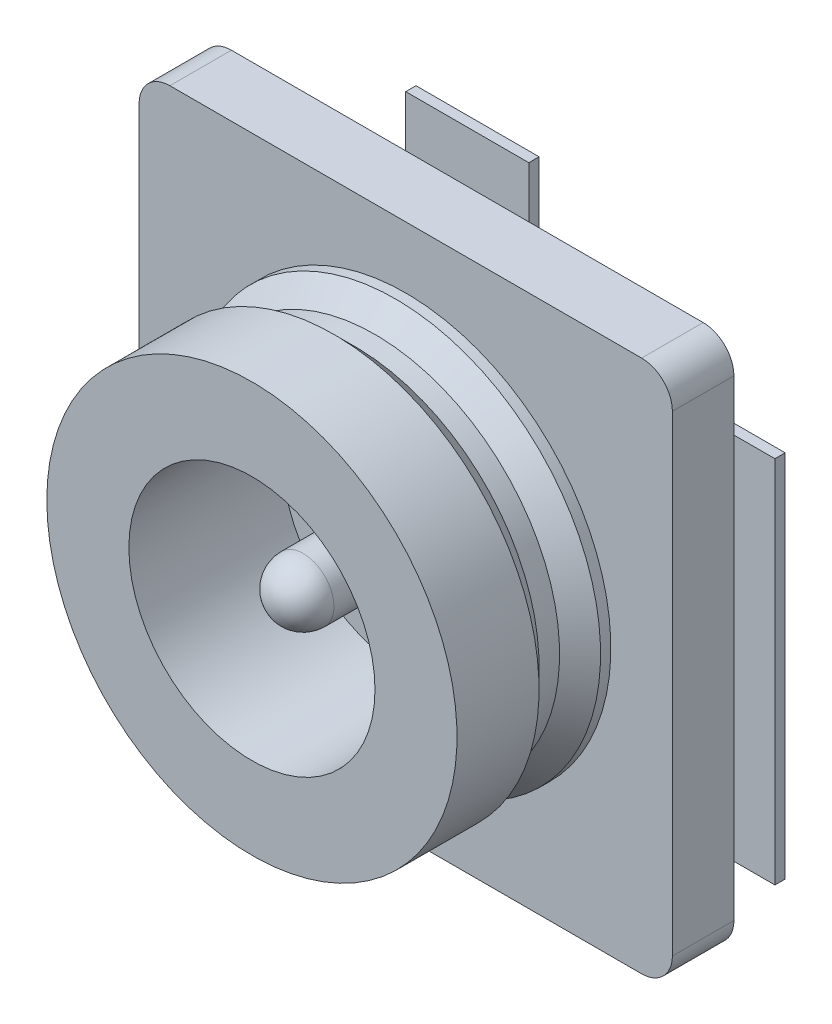
SolidWorks part; units mm, degrees
ref_plane "Front Plane" through (0, 0, 0) normal (0, 0, 1) x (1, 0, 0)
ref_plane "Top Plane" through (0, 0, 0) normal (0, 1, 0) x (1, 0, 0)
ref_plane "Right Plane" through (0, 0, 0) normal (1, 0, 0) x (0, 0, -1)
sketch "Sketch2" plane through (0, 0, 0) normal (0, 0, 1) x (1, 0, 0)
  line L1 (0, 0) -> (2.6, 0)
  line L2 (0, 0) -> (0, 2.6)
  line L3 (0, 2.6) -> (2.6, 2.6)
  line L4 (2.6, 0) -> (2.6, 2.6)
  dimension "D1" = 2.6
  dimension "D2" = 2.6
extrude "Boss-Extrude2" add sketch "Sketch2" along normal blind 0.3
fillet "Fillet1" radius 0.15 4 edges at (0, 0, 0.15) (2.6, 0, 0.15) (0, 2.6, 0.15) (2.6, 2.6, 0.15)
ref_plane "Plane1" through (0, 1.3, 0) normal (0, 1, 0) x (1, 0, 0)
ref_plane "Plane2" through (1.3, 0, 0) normal (1, 0, 0) x (0, 0, -1)
ref_axis "Axis1" through (1.3, 1.3, -0.0175) along (0, 0, -1)
sketch "Sketch3" plane through (0, 0, 0) normal (0, 0, 1) x (1, 0, 0)
  line L0 (0, 1.3) -> (2.6, 1.3) construction
  line L1 (-0.2, 2.2) -> (0.3, 2.2)
  line L2 (-0.2, 2.2) -> (-0.2, 0.4)
  line L3 (-0.2, 0.4) -> (0.3, 0.4)
  line L4 (0.3, 2.2) -> (0.3, 0.4)
  line L5 (2.3, 2.2) -> (2.8, 2.2)
  line L6 (2.3, 2.2) -> (2.3, 0.4)
  line L7 (2.3, 0.4) -> (2.8, 0.4)
  line L8 (2.8, 2.2) -> (2.8, 0.4)
  line L9 (0, 2.45) -> (0, 0.15) construction
  line L10 (2.6, 0.15) -> (2.6, 2.45) construction
  line L11 (1.475, 2.2) -> (1.6, 2.2)
  line L12 (2.45, 2.6) -> (0.15, 2.6) construction
  line L13 (1.3, 2.6) -> (1.3, 0) construction
  line L14 (0.15, 0) -> (2.45, 0) construction
  line L15 (1, 2.85) -> (1.6, 2.85)
  line L16 (1, 2.85) -> (1, 2.2)
  line L17 (1, 2.2) -> (1.125, 2.2)
  line L18 (1.6, 2.85) -> (1.6, 2.2)
  line L19 (1, 0.4) -> (1.6, 0.4)
  line L20 (1, 0.4) -> (1, -0.25)
  line L21 (1, -0.25) -> (1.6, -0.25)
  line L22 (1.6, 0.4) -> (1.6, -0.25)
  line L24 (1.125, 2.2) -> (1.125, 1.5437)
  line L26 (1.475, 2.2) -> (1.475, 1.5437)
  arc A0 (1.125, 1.5437) -> (1.475, 1.5437) centre (1.3, 1.3) ccw
  point P14 (2.3, 1.3)
  point P21 (0.3, 1.3)
  point P33 (1.3, 0.4)
  dimension "D6" = 0.6
  dimension "D1" = 3
  dimension "D2" = 0.5
  dimension "D3" = 0.5
  dimension "D4" = 1.8
  dimension "D5" = 0.6
  dimension "D7" = 3.1
  dimension "D8" = 0.35
extrude "Boss-Extrude3" add sketch "Sketch3" against normal blind 0.05
sketch "Sketch4" plane through (1.3, 0, 0) normal (1, 0, 0) x (0, 0, -1)
  line L0 (-0.3, 0.15) -> (-0.3, 2.45) construction
  line L1 (-0.3, 1.45) -> (-0.8, 1.45)
  line L2 (-0.3, 1.45) -> (-0.3, 1.3)
  line L3 (-0.3, 2.6) -> (-0.3, 2.45) construction
  line L4 (-0.95, 1.3) -> (-0.3, 1.3)
  line L5 (0.0607, 1.3) -> (-0.95, 1.3) construction
  line L6 (0.0175, 1.3) -> (0.3675, 1.3) construction
  line L7 (-0.3, 1.9) -> (-1.05, 1.9)
  line L8 (-0.3, 1.9) -> (-0.3, 2.3)
  line L9 (-0.3, 2.3) -> (-0.35, 2.3)
  line L10 (-1.05, 1.9) -> (-1.05, 2.3)
  line L11 (-0.55, 2.2) -> (-0.65, 2.3)
  line L14 (-0.45, 2.2) -> (-0.55, 2.2)
  line L16 (-0.45, 2.2) -> (-0.35, 2.3)
  line L17 (-0.65, 2.3) -> (-1.05, 2.3)
  arc A0 (-0.8, 1.45) -> (-0.95, 1.3) centre (-0.8, 1.3) ccw
  dimension "D5" = 0.15
  dimension "D1" = 1
  dimension "D2" = 0.6
  dimension "D3" = 0.75
  dimension "D4" = 0.65
  dimension "D6" = 225
  dimension "D7" = 225
  dimension "D8" = 0.1
  dimension "D9" = 0.1
  dimension "D10" = 0.05
revolve "Revolve1" add sketch "Sketch4" angle 360 about L5
